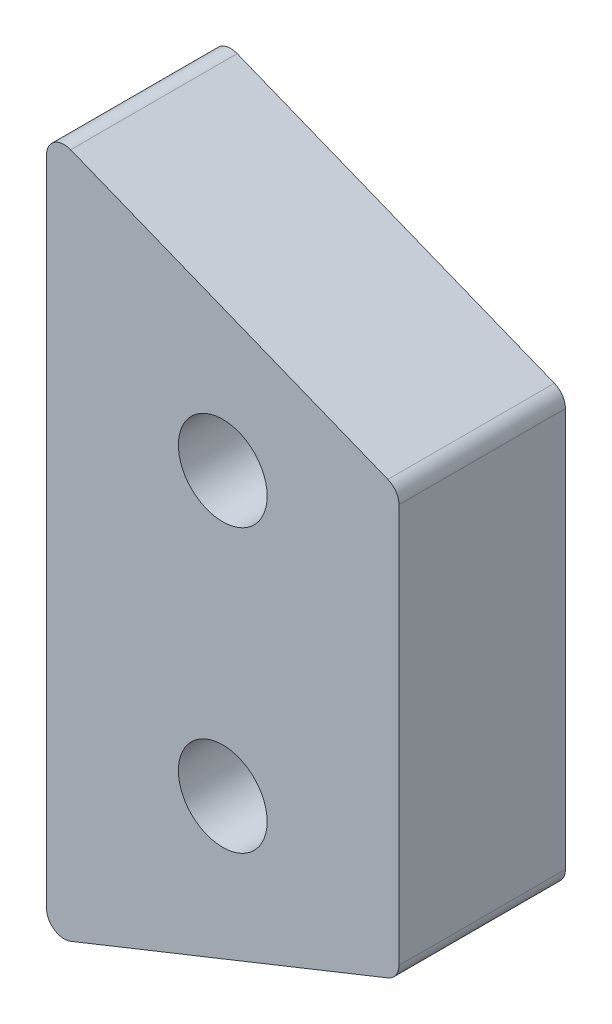
SolidWorks part; units mm, degrees
ref_plane "Front Plane" through (0, 0, 0) normal (0, 0, 1) x (1, 0, 0)
ref_plane "Top Plane" through (0, 0, 0) normal (0, 1, 0) x (1, 0, 0)
ref_plane "Right Plane" through (0, 0, 0) normal (1, 0, 0) x (0, 0, -1)
sketch "Sketch1" plane through (0, 0, 0) normal (0, 0, 1) x (1, 0, 0)
  line L0 (0, 0) -> (15.875, -6.35)
  line L1 (15.875, -6.35) -> (15.875, -25.4)
  line L2 (15.875, -25.4) -> (0, -31.75)
  line L3 (0, -31.75) -> (0, 0)
  line L4 (7.9375, -3.175) -> (7.9375, -9.525) construction
  line L5 (7.9375, -9.525) -> (7.9375, -22.225) construction
  line L6 (7.9375, -22.225) -> (7.9375, -28.575) construction
  circle A0 centre (7.9375, -22.225) radius 2
  circle A1 centre (7.9375, -9.525) radius 2
  dimension "D4" = 4
  dimension "D1" = 31.75
  dimension "D2" = 19.05
  dimension "D3" = 15.875
  dimension "D5" = 9.525
extrude "Boss-Extrude1" add sketch "Sketch1" along normal blind 7.5
fillet "Fillet1" radius 0.7937 4 edges at (0, -31.75, 3.75) (15.875, -25.4, 3.75) (15.875, -6.35, 3.75) (0, 0, 3.75)
sketch "Sketch2" plane through (0, 0, 7.5) normal (0, 0, 1) x (1, 0, 0)
  line L0 (14.6875, -22.225) -> (14.6875, -25.875)
  line L1 (1.0885, -31.3146) -> (15.376, -25.5996) construction
  line L2 (1.1875, -22.225) -> (1.1875, -31.275)
  line L3 (1.1875, -31.275) -> (14.6875, -25.875)
  arc A0 (14.6875, -22.225) -> (1.1875, -22.225) centre (7.9375, -22.225) ccw
  dimension "D1" = 13.5
extrude "Cut-Extrude1" cut sketch "Sketch2" against normal blind 4.25
mirror "Mirror1" about plane through (0, 0, 0) normal (0, 0, -1) of bodies 102
delete or keep bodies "Body-Delete/Keep 1" type delete bodies bodies 102
